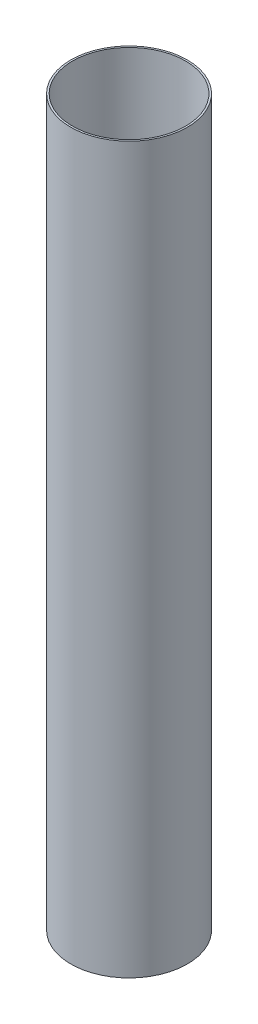
SolidWorks part; units mm, degrees
ref_plane "Front Plane" through (0, 0, 0) normal (0, 0, 1) x (1, 0, 0)
ref_plane "Top Plane" through (0, 0, 0) normal (0, 1, 0) x (1, 0, 0)
ref_plane "Right Plane" through (0, 0, 0) normal (1, 0, 0) x (0, 0, -1)
sketch "Sketch1" plane through (0, 0, 0) normal (0, 1, 0) x (1, 0, 0)
  circle A0 centre (0, 0) radius 51.1048
  circle A1 centre (0, 0) radius 49.53
  dimension "D1" = 102.2096
  dimension "D2" = 99.06
extrude "Boss-Extrude1" add sketch "Sketch1" along normal blind 635
equation "\"Body_Tube_OD\"= 4.024in"
equation "\"Body_Tube_ID\"= 3.90in"
equation "\"D1@Sketch1\"=\"Body_Tube_OD\""
equation "\"D2@Sketch1\"=\"Body_Tube_ID\""
equation "\"Fwd_Section_Length\" = 25in"
equation "\"D1@Boss-Extrude1\"=\"Fwd_Section_Length\""
